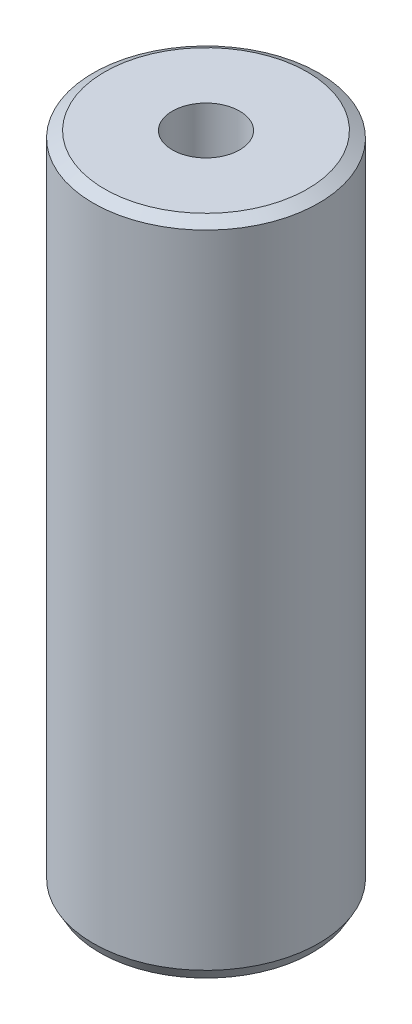
SolidWorks part; units mm, degrees
ref_plane "Front Plane" through (0, 0, 0) normal (0, 0, 1) x (1, 0, 0)
ref_plane "Top Plane" through (0, 0, 0) normal (0, 1, 0) x (1, 0, 0)
ref_plane "Right Plane" through (0, 0, 0) normal (1, 0, 0) x (0, 0, -1)
sketch "Sketch1" plane through (0, 0, 0) normal (0, 1, 0) x (1, 0, 0)
  circle A0 centre (0, 0) radius 32.5
  dimension "SHAFT_OD" = 65
extrude "Boss-Extrude1" add sketch "Sketch1" along normal blind 189.8984
sketch "Sketch2" plane through (0, 0, 0) normal (0, 1, 0) x (1, 0, 0)
  circle A0 centre (0, 0) radius 9.6993
  dimension "BORE_D" = 19.3986
extrude "Cut-Extrude1" cut sketch "Sketch2" along normal through all
chamfer "Chamfer1" distance 1.8853 angle 60 2 edges at (0, 189.8984, 32.5) (0, 0, 32.5) first distance on face at (0, 189.8984, 32.5) first distance on face at (0, 0, 9.6993)
